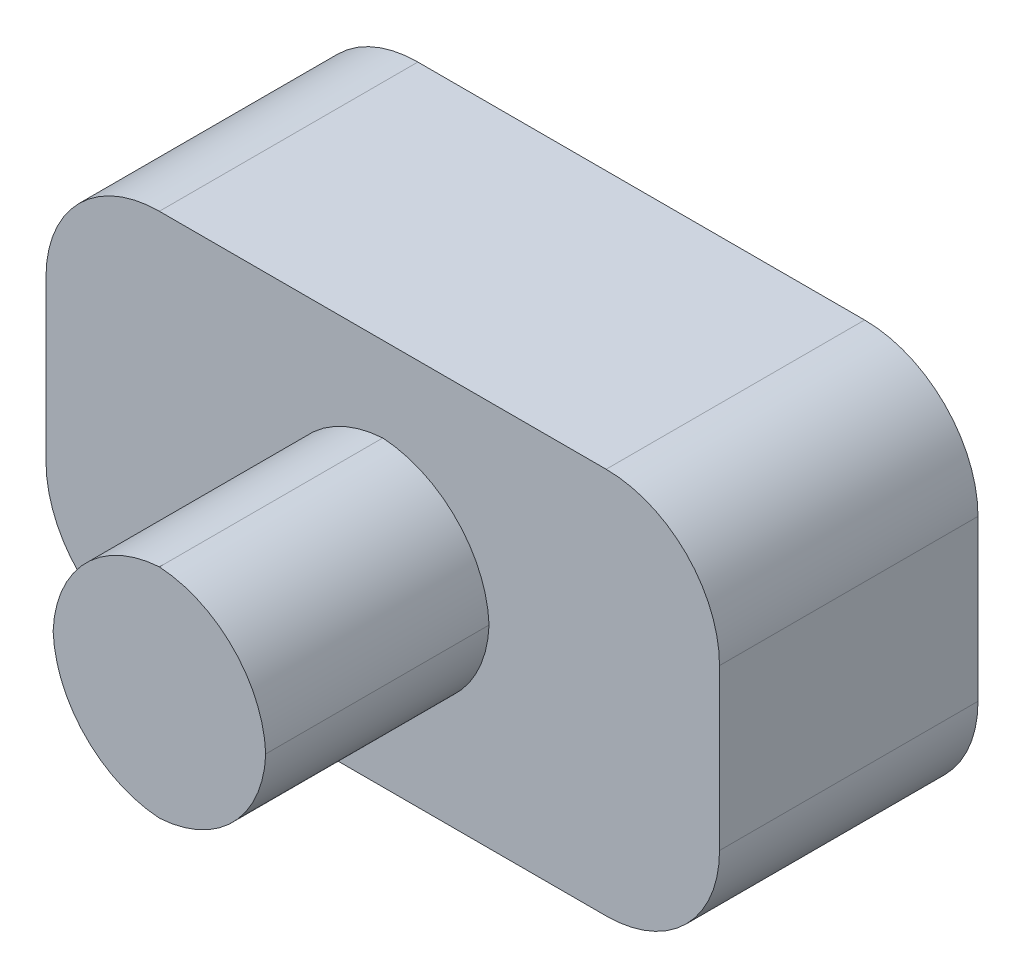
SolidWorks part; units mm, degrees
note: The reader was unsure of these and kept them because the rebuilt part matched: shared geometry of "Sketch1<4>".
ref_plane "Front Plane" through (0, 0, 0) normal (0, 0, 1) x (1, 0, 0)
ref_plane "Top Plane" through (0, 0, 0) normal (0, 1, 0) x (1, 0, 0)
ref_plane "Right Plane" through (0, 0, 0) normal (1, 0, 0) x (0, 0, -1)
sketch "Sketch1" plane through (0, 0, 0) normal (0, 0, 1) x (1, 0, 0)
  line L1 (-75.4515, 43.3403) -> (75.4515, 43.3403)
  line L2 (-75.4515, 43.3403) -> (-75.4515, -43.3403)
  line L3 (-75.4515, -43.3403) -> (75.4515, -43.3403)
  line L4 (75.4515, 43.3403) -> (75.4515, -43.3403)
  line L5 (-75.4515, 43.3403) -> (75.4515, -43.3403) construction
  line L6 (-75.4515, -43.3403) -> (75.4515, 43.3403) construction
  line L7 (-23.8371, 24.4281) -> (23.8371, 24.4281)
  line L8 (-23.8371, 24.4281) -> (-23.8371, -24.4281)
  line L9 (-23.8371, -24.4281) -> (23.8371, -24.4281)
  line L10 (23.8371, 24.4281) -> (23.8371, -24.4281)
  line L11 (-23.8371, 24.4281) -> (23.8371, -24.4281) construction
  line L12 (-23.8371, -24.4281) -> (23.8371, 24.4281) construction
  circle A0 centre (0, 0) radius 15.8889
extrude "Boss-Extrude1" add sketch "Sketch1" along normal blind 50.038 contours L4 L1 L2 L3 L7 L10 L9 L8
extrude "Boss-Extrude2" add sketch "Sketch1<4>" against normal blind 57.912 separate body contours L4 L1 L2 L3 L7 L10 L9 L8
sketch "Sketch1<4>" plane through (0, 0, 0) normal (0, 0, 1) x (1, 0, 0) same geometry as "Sketch1"
fillet "Fillet1" radius 25.4 8 edges at (-23.8371, 24.4281, -28.956) (23.8371, 24.4281, -28.956) (23.8371, -24.4281, -28.956) (-23.8371, -24.4281, -28.956) (-75.4515, 43.3403, -28.956) (-75.4515, -43.3403, -28.956) (75.4515, -43.3403, -28.956) (75.4515, 43.3403, -28.956)
fillet "Fillet2" radius 25.4 4 edges at (23.8371, 24.4281, 25.019) (-23.8371, 24.4281, 25.019) (23.8371, -24.4281, 25.019) (-23.8371, -24.4281, 25.019)
scale "Scale2" bodies to scale 102 101 scale about origin uniform scaling yes scale factor 0.4
